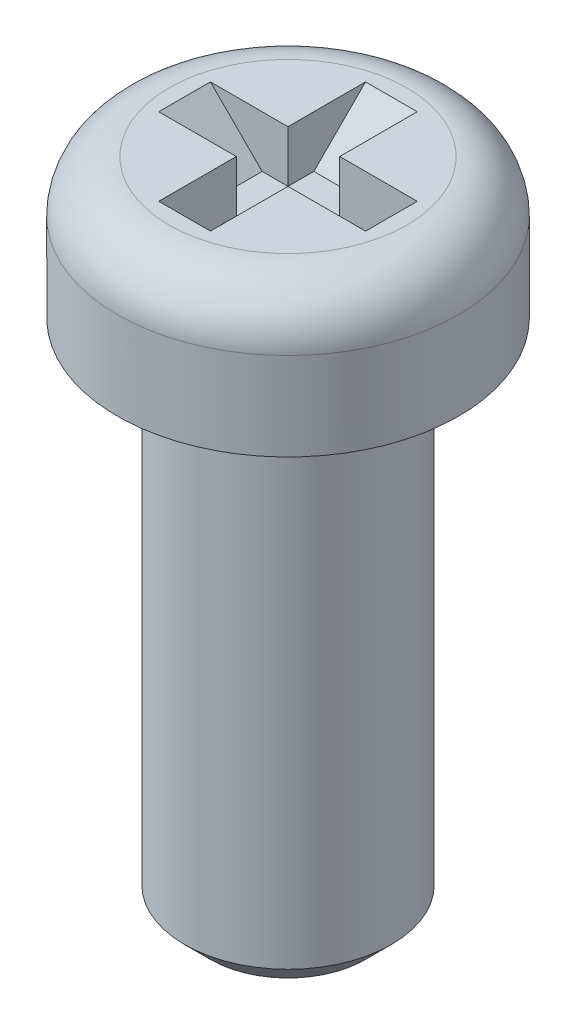
SolidWorks part; units mm, degrees
ref_plane "前视基准面" through (0, 0, 0) normal (0, 0, 1) x (1, 0, 0)
ref_plane "上视基准面" through (0, 0, 0) normal (0, 1, 0) x (1, 0, 0)
ref_plane "右视基准面" through (0, 0, 0) normal (1, 0, 0) x (0, 0, -1)
other "Configuration Table"
sketch "草图1" plane through (0, 0, 0) normal (0, 1, 0) x (1, 0, 0)
  circle A0 centre (0, 0) radius 2
  dimension "D1" = 4
extrude "凸台-拉伸1" add sketch "草图1" along normal blind 10
cosmetic thread "装饰螺纹线1" parameters "D2"=3
sketch "草图2" plane through (0, 10, 0) normal (0, 1, 0) x (1, 0, 0)
  circle A0 centre (0, 0) radius 3.3
  dimension "D1" = 6.6
extrude "凸台-拉伸2" add sketch "草图2" along normal blind 2.7
fillet "圆角1" radius 1 1 edges at (0, 12.7, 3.3)
chamfer "倒角1" distance 0.5 angle 45 1 edges at (0, 0, 2)
sketch "草图3" plane through (0, 12.7, 0) normal (0, 1, 0) x (1, 0, 0)
  line L0 (-2, 0) -> (2, 0)
  line L1 (0, 2) -> (0, -2)
  point P5 (0, 0)
  point P9 (0, 0)
  dimension "D1" = 4
  dimension "D2" = 4
extrude "切除-拉伸-薄壁1" cut sketch "草图3" against normal blind 1 thin thin type mid plane wall 1
chamfer "倒角2" distance 1 angle 45 4 edges at (0, 11.7, 2) (2, 11.7, 0) (0, 11.7, -2) (-2, 11.7, 0)
